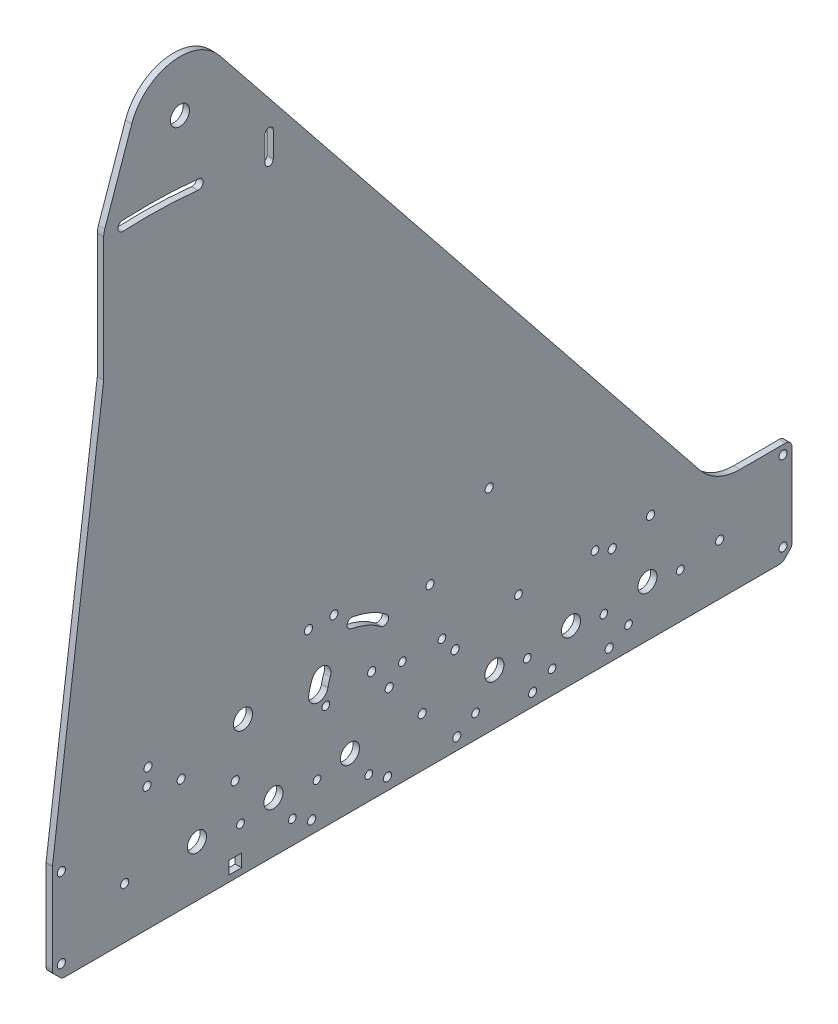
SolidWorks part; units mm, degrees
ref_plane "Front Plane" through (0, 0, 0) normal (0, 0, 1) x (1, 0, 0)
ref_plane "Top Plane" through (0, 0, 0) normal (0, 1, 0) x (1, 0, 0)
ref_plane "Right Plane" through (0, 0, 0) normal (1, 0, 0) x (0, 0, -1)
sketch "Sketch1" plane through (0, 0, 0) normal (1, 0, 0) x (0, 0, -1)
  line L0 (-184.15, -24.6062) -> (184.15, -24.6062)
  line L1 (184.15, -24.6062) -> (184.15, 26.1938)
  line L2 (184.15, 26.1938) -> (146.05, 26.1937)
  line L5 (-145.839, 321.5609) -> (-184.15, 26.1938)
  line L6 (-184.15, 26.1938) -> (-184.15, -24.6062)
  line L7 (-184.15, 350.0437) -> (184.15, 350.0437) construction
  line L9 (146.05, 26.1937) -> (-100.8314, 334.1803)
  arc A0 (-100.8314, 334.1803) -> (-145.839, 321.5609) centre (-120.65, 318.2937) ccw
  point P8 (0, -24.6062)
  dimension "D1" = 368.3
  dimension "D7" = 25.4
  dimension "D2" = 50.8
  dimension "D3" = 38.1
  dimension "D4" = 24.6062
  dimension "D5" = 374.65
  dimension "D6" = 304.8
  dimension "D8" = 342.9
extrude "Boss-Extrude1" add sketch "Sketch1" along normal blind 3.175
chamfer "Chamfer1" distance 4.7625 angle 45 2 edges at (1.5875, -24.6062, 184.15) (1.5875, -24.6062, -184.15)
fillet "Fillet1" radius 25.4 1 edges at (1.5875, 26.1937, -146.05)
fillet "Fillet2" radius 3.175 2 edges at (1.5875, 26.1938, 184.15) (1.5875, 26.1938, -184.15)
fillet "Fillet3" radius 3.175 4 edges at (1.5875, -19.8438, -184.15) (1.5875, -24.6062, -179.3875) (1.5875, -19.8437, 184.15) (1.5875, -24.6062, 179.3875)
sketch "Sketch30" plane through (3.175, 0, 0) normal (1, 0, 0) x (0, 0, -1)
  circle A8 centre (-89.211, 42.2593) radius 4.7625
  circle A9 centre (-25.1593, 30.6938) radius 2.032
  arc A10 (-51.7173, 35.4892) -> (-50.2741, 40.5715) centre (-25.1593, 30.6938) cw construction
  arc A11 (-54.7652, 42.3379) -> (-56.4665, 36.3468) centre (-25.1593, 30.6938) ccw
  arc A12 (-45.783, 38.8051) -> (-46.9681, 34.6317) centre (-25.1593, 30.6938) ccw
  arc A13 (-45.783, 38.8051) -> (-54.7652, 42.3379) centre (-50.2741, 40.5715) ccw
  arc A14 (-56.4665, 36.3468) -> (-46.9681, 34.6317) centre (-51.7173, 35.4892) ccw
  arc A15 (-34.9881, 56.6661) -> (-19.1131, 49.8125) centre (-41.7582, 19.1724) cw construction
  arc A16 (-17.6789, 51.753) -> (-34.5594, 59.0407) centre (-41.7582, 19.1724) ccw
  arc A17 (-20.5473, 47.8719) -> (-35.4169, 54.2915) centre (-41.7582, 19.1724) ccw
  arc A18 (-20.5473, 47.8719) -> (-17.6789, 51.753) centre (-19.1131, 49.8125) ccw
  arc A19 (-34.5594, 59.0407) -> (-35.4169, 54.2915) centre (-34.9881, 56.6661) ccw
  arc A20 (-19.1131, 49.8125) -> (-34.9881, 56.6661) centre (-41.7582, 19.1724) ccw construction
  circle A21 centre (94.6345, 23.8125) radius 2.032
  circle A22 centre (-56.6241, 64.5541) radius 2.032
  circle A23 centre (-43.9241, 64.5541) radius 2.032
  circle A24 centre (-56.6241, 64.5541) radius 1.905 construction
  circle A25 centre (-43.9241, 64.5541) radius 1.905 construction
  point P7 (-51.1204, 38.0658)
  point P19 (-26.6567, 54.1518)
  dimension "D2" = 9.652
  dimension "D4" = 4.064
  dimension "D1" = 4.064
  dimension ".375" = 9.525
  dimension "D3" = 4.826
extrude "Cut-Extrude9" cut sketch "Sketch30" against normal through all
sketch "Sketch16" plane through (3.175, 0, 0) normal (1, 0, 0) x (0, 0, -1)
  circle A0 centre (112.1746, 0.7937) radius 4.7625
  circle A1 centre (74.0746, 0.7937) radius 4.7625
  circle A2 centre (35.9746, 0.7937) radius 4.7625
  circle A3 centre (-35.9746, 0.7938) radius 4.7625
  circle A4 centre (-74.0746, 0.7938) radius 4.7625
  circle A5 centre (-112.1746, 0.7937) radius 4.7625
  dimension "D1" = 9.525
  dimension "D2" = 9.525
extrude "Cut-Extrude1" cut sketch "Sketch16" against normal up to next
sketch "Sketch25" plane through (3.175, 0, 0) normal (1, 0, 0) x (0, 0, -1)
  circle A0 centre (102.7672, -13.0003) radius 1.905 construction
  circle A1 centre (86.0486, 27.3622) radius 1.905 construction
  circle A2 centre (128.5804, -2.3081) radius 1.905 construction
  circle A3 centre (102.7672, -13.0003) radius 1.905
  circle A4 centre (86.0486, 27.3622) radius 1.905
  circle A5 centre (128.5804, -2.3081) radius 1.905
  circle A6 centre (64.6672, -13.0003) radius 1.905 construction
  circle A8 centre (-9.8486, 27.3622) radius 1.905 construction
  circle A10 centre (-47.9486, 27.3622) radius 1.905 construction
  circle A11 centre (-90.4804, -2.3081) radius 1.905 construction
  circle A12 centre (-64.6672, -13.0003) radius 1.905 construction
  circle A14 centre (-52.3804, -2.3081) radius 1.905 construction
  circle A15 centre (-26.5672, -13.0003) radius 1.905 construction
  circle A16 centre (9.8486, 27.3622) radius 1.905 construction
  circle A17 centre (26.5672, -13.0003) radius 1.905 construction
  circle A18 centre (47.9486, 27.3622) radius 1.905 construction
  circle A19 centre (52.3804, -2.3081) radius 1.905 construction
  circle A20 centre (90.4804, -2.3081) radius 1.905 construction
  circle A21 centre (-9.8486, 27.3622) radius 1.905
  circle A23 centre (-47.9486, 27.3622) radius 1.905
  circle A24 centre (-90.4804, -2.3081) radius 1.905
  circle A25 centre (-64.6672, -13.0003) radius 1.905
  circle A27 centre (-52.3804, -2.3081) radius 1.905
  circle A28 centre (-26.5672, -13.0003) radius 1.905
  circle A29 centre (9.8486, 27.3622) radius 1.905
  circle A30 centre (26.5672, -13.0003) radius 1.905
  circle A31 centre (47.9486, 27.3622) radius 1.905
  circle A32 centre (64.6672, -13.0003) radius 1.905
  circle A33 centre (52.3804, -2.3081) radius 1.905
  circle A34 centre (90.4804, -2.3081) radius 1.905
extrude "Cut-Extrude4" cut sketch "Sketch25" against normal up to next
sketch "Sketch23" plane through (3.175, 0, 0) normal (1, 0, 0) x (0, 0, -1)
  circle A0 centre (179.705, 21.7488) radius 1.905 construction
  point P0 (-55.0246, -18.3223)
  point P6 (-93.1246, 17.5943)
  point P9 (-17.2515, -18.6426)
  point P12 (-16.4124, 19.3854)
  point P15 (16.4124, 19.3854)
  point P18 (17.2515, -18.6426)
  point P21 (55.0246, -18.3223)
  point P35 (3.8736, 53.6853)
  point P38 (113.7728, 28.6594)
  point P41 (-137.0088, 37.226)
  point P44 (-179.705, 21.7487)
  point P47 (-179.705, -18.0026)
  point P50 (179.705, 21.7488)
  point P53 (179.705, -18.0026)
  point P59 (93.1246, -18.3223)
hole_wizard "#8 (0.16) Diameter Hole1" positions "Sketch23" profile "Sketch24" hole size "#8" standard "ANSI Inch" end condition up to next
sketch "Sketch24" plane through (3.175, -18.3223, 55.0246) normal (0, 1, 0) x (0, 0, -1)
  line L0 (0, 0) -> (0, 3.175)
  line L1 (0, 3.175) -> (2.032, 3.175)
  line L2 (2.032, 3.175) -> (2.032, 0)
  line L5 (2.032, 0) -> (0, 0)
  line L11 (0, -6.35) -> (0, 107.95) construction
  dimension "Thru Hole Dia." = 4.064
  dimension "Thru Hole Depth" = 3.175
sketch "Sketch22" plane through (3.175, 0, 0) normal (1, 0, 0) x (0, 0, -1)
  line L0 (-96.2996, -15.1473) -> (-89.9496, -15.1473) construction
  line L1 (-96.2996, -15.1473) -> (-89.9496, -15.1473)
  line L2 (-96.2996, -15.1473) -> (-96.2996, -21.4973)
  line L3 (-96.2996, -21.4973) -> (-89.9496, -21.4973)
  line L4 (-89.9496, -15.1473) -> (-89.9496, -21.4973)
  line L5 (-96.2996, -15.1473) -> (-89.9496, -21.4973) construction
  line L6 (-96.2996, -21.4973) -> (-89.9496, -15.1473) construction
  line L7 (-89.9496, -15.1473) -> (-89.9496, -19.8734) construction
  point P0 (-93.1246, -18.3223)
  dimension "D1" = 6.35
extrude "Cut-Extrude3" cut sketch "Sketch22" against normal up to next
sketch "Sketch21" plane through (3.175, 0, 0) normal (1, 0, 0) x (0, 0, -1)
  circle A0 centre (-148.1579, 0.7937) radius 2.032
  circle A2 centre (0, 0) radius 2.032
  circle A3 centre (148.1579, 0.7938) radius 2.032
  dimension "D1" = 4.064
extrude "Cut-Extrude2" cut sketch "Sketch21" against normal up to next
sketch "Sketch26" [suppressed] plane through (3.175, 0, 0) normal (1, 0, 0) x (0, 0, -1)
  line L0 (-145.839, 321.5609) -> (-184.1236, 26.3971) construction
  line L1 (-178.0724, -24.6062) -> (178.0724, -24.6062) construction
  circle A0 centre (-121.0218, 216.6937) radius 15.24
  dimension "D1" = 30.48
  dimension "D2" = 38.1
  dimension "D3" = 241.3
extrude "Cut-Extrude5" [suppressed] cut sketch "Sketch26" against normal through all
sketch "Sketch27" plane through (3.175, 0, 0) normal (1, 0, 0) x (0, 0, -1)
  circle A0 centre (-120.65, 318.2937) radius 4.7625
  dimension "D1" = 9.525
extrude "Cut-Extrude6" cut sketch "Sketch27" against normal through all
sketch "Sketch28" plane through (3.175, 0, 0) normal (1, 0, 0) x (0, 0, -1)
  line L0 (-120.65, 318.2937) -> (-103.5612, 277.2599) construction
  line L1 (-103.5612, 277.2599) -> (-86.3654, 258.566) construction
  line L2 (-86.3654, 258.566) -> (-90.1612, 246.4465) construction
  line L3 (-90.1612, 246.4465) -> (-93.9569, 234.327) construction
  line L4 (-145.839, 321.5609) -> (-184.1236, 26.3971) construction
  circle A0 centre (-93.9569, 234.327) radius 2.032
  circle A1 centre (-90.1612, 246.4465) radius 2.032
  circle A2 centre (-86.3654, 258.566) radius 2.0955
  circle A3 centre (-103.5612, 277.2599) radius 2.032
  dimension "D4" = 4.064
  dimension "D5" = 4.191
  dimension "D6" = 4.064
  dimension "D1" = 25.4
  dimension "D2" = 44.45
  dimension "D3" = 12.7
  dimension "D7" = 30
  dimension "D8" = 120
  dimension "D9" = 160
extrude "Cut-Extrude7" [suppressed] cut sketch "Sketch28" against normal through all
sketch "Sketch29" plane through (3.175, 0, 0) normal (1, 0, 0) x (0, 0, -1)
  line L1 (-76.2, 288.925) -> (-76.2, 276.225) construction
  line L2 (-74.168, 288.925) -> (-74.168, 276.225)
  line L3 (-78.232, 288.925) -> (-78.232, 276.225)
  arc A4 (-74.168, 288.925) -> (-78.232, 288.925) centre (-76.2, 288.925) ccw
  arc A5 (-78.232, 276.225) -> (-74.168, 276.225) centre (-76.2, 276.225) ccw
  point P8 (-76.2, 282.575)
  dimension "D1" = 276.225
  dimension "D2" = 2.032
  dimension "D3" = 76.2
  dimension "D4" = 12.7
sketch "Sketch31" plane through (0, 0, 0) normal (-1, 0, 0) x (0, 0, 1)
extrude "Cut-Extrude10" [suppressed] cut sketch "Sketch31" against normal through all
sketch "Sketch34" plane through (0, 0, 0) normal (-1, 0, 0) x (0, 0, 1)
  line L3 (123.9045, 95.7355) -> (127.1716, 70.5465) construction
  line L4 (126.0455, 96.0132) -> (129.3127, 70.8242)
  line L5 (121.7634, 95.4578) -> (125.0306, 70.2688)
  line L6 (145.839, 321.5609) -> (184.1236, 26.3971) construction
  arc A2 (126.0455, 96.0132) -> (121.7634, 95.4578) centre (123.9045, 95.7355) ccw
  arc A3 (125.0306, 70.2688) -> (129.3127, 70.8242) centre (127.1716, 70.5465) ccw
  point P9 (125.538, 83.141)
  dimension "D8" = 4.318
  dimension "D6" = 50.8
  dimension "D7" = 25.4
extrude "Cut-Extrude12" [suppressed] cut sketch "Sketch34" against normal through all
sketch "Sketch38" plane through (3.175, 0, 0) normal (1, 0, 0) x (0, 0, -1)
  line L0 (-184.15, 25.9887) -> (-184.15, -18.5286) construction
  line L1 (-178.0724, -24.6062) -> (178.0724, -24.6062) construction
  circle A0 centre (-136.525, 45.2437) radius 2.032
  dimension "D1" = 47.625
  dimension "D3" = 4.064
  dimension "D2" = 69.85
extrude "Cut-Extrude14" cut sketch "Sketch38" against normal through all
sketch "Sketch37" plane through (3.175, 0, 0) normal (1, 0, 0) x (0, 0, -1)
  circle A0 centre (33.3375, 80.645) radius 2.032
  circle A8 centre (0, 0) radius 2.032 construction
  dimension "D1" = 4.064
  dimension "D2" = 33.3375
  dimension "D3" = 80.645
extrude "Cut-Extrude13" cut sketch "Sketch37" against normal through all
extrude "Cut-Extrude15" cut sketch "Sketch29" against normal through all
sketch "Sketch40" plane through (3.175, 0, 0) normal (1, 0, 0) x (0, 0, -1)
  circle A0 centre (-120.015, 31.75) radius 2.032
  dimension "D1" = 4.064
  dimension "D2" = 120.015
  dimension "D3" = 31.75
extrude "Cut-Extrude16" cut sketch "Sketch40" against normal through all
sketch "Sketch41" [suppressed] plane through (3.175, 0, 0) normal (1, 0, 0) x (0, 0, -1)
  line L0 (-120.65, 318.2937) -> (-98.425, 279.7989) construction
  line L1 (-98.425, 279.7989) -> (-77.6666, 265.1617) construction
  line L2 (-120.65, 318.2937) -> (-60.41, 318.2937) construction
  circle A0 centre (-120.65, 318.2937) radius 25.4 construction
  circle A1 centre (-98.425, 279.7989) radius 19.05 construction
  circle A2 centre (-77.6666, 265.1617) radius 6.35 construction
  circle A3 centre (-98.425, 279.7989) radius 2.032
  circle A4 centre (-77.6666, 265.1617) radius 2.032
  dimension "D1" = 50.8
  dimension "D2" = 38.1
  dimension "D3" = 12.7
  dimension "D4" = 4.064
  dimension "D5" = 60
extrude "Cut-Extrude17" [suppressed] cut sketch "Sketch41" against normal through all
sketch "Sketch43" plane through (3.175, 0, 0) normal (1, 0, 0) x (0, 0, -1)
  line L0 (-152.4, 200.025) -> (-123.6487, 200.025) construction
  line L1 (-115.9779, 252.0412) -> (-152.4, 200.025) construction
  circle A0 centre (-152.4, 200.025) radius 2.032
  arc A1 (-143.2813, 262.8669) -> (-96.4668, 230.087) centre (-152.4, 200.025) cw construction
  arc A2 (-92.2158, 232.3717) -> (-142.5883, 267.6428) centre (-152.4, 200.025) ccw
  arc A3 (-100.7177, 227.8023) -> (-143.9743, 258.0909) centre (-152.4, 200.025) ccw
  arc A4 (-100.7177, 227.8023) -> (-92.2158, 232.3717) centre (-96.4668, 230.087) ccw
  arc A5 (-142.5883, 267.6428) -> (-143.9743, 258.0909) centre (-143.2813, 262.8669) ccw
  point P6 (-115.9779, 252.0412)
  dimension "D1" = 4.064
  dimension "D4" = 4.826
  dimension "D2" = 200.025
  dimension "D3" = 152.4
  dimension "D5" = 63.5
  dimension "D6" = 57.15
  dimension "D7" = 55
extrude "Cut-Extrude19" [suppressed] cut sketch "Sketch43" against normal through all
sketch "Sketch44" plane through (3.175, 0, 0) normal (1, 0, 0) x (0, 0, -1)
  circle A0 centre (-142.875, 226.3775) radius 2.032
  dimension "D1" = 4.064
  dimension "D2" = 142.875
  dimension "D3" = 226.3775
extrude "Cut-Extrude20" [suppressed] cut sketch "Sketch44" against normal through all
sketch "Sketch50" plane through (0, 0, 0) normal (-1, 0, 0) x (0, 0, 1)
  line L0 (89.6567, 207.1688) -> (64.2567, 207.1688) construction
  line L1 (89.6567, 205.1368) -> (64.2567, 205.1368)
  line L2 (89.6567, 209.2008) -> (64.2567, 209.2008)
  line L3 (64.2567, 194.4688) -> (38.8567, 194.4688) construction
  line L4 (64.2567, 192.4368) -> (38.8567, 192.4368)
  line L5 (64.2567, 196.5008) -> (38.8567, 196.5008)
  arc A1 (89.6567, 205.1368) -> (89.6567, 209.2008) centre (89.6567, 207.1688) ccw
  arc A2 (64.2567, 209.2008) -> (64.2567, 205.1368) centre (64.2567, 207.1688) ccw
  arc A3 (64.2567, 192.4368) -> (64.2567, 196.5008) centre (64.2567, 194.4688) ccw
  arc A4 (38.8567, 196.5008) -> (38.8567, 192.4368) centre (38.8567, 194.4688) ccw
  point P3 (76.9567, 207.1688)
  point P5 (51.5567, 194.4688)
  dimension "D1" = 2.032
  dimension "D2" = 207.1688
  dimension "D3" = 89.6567
  dimension "D4" = 25.4
  dimension "D5" = 12.7
extrude "Cut-Extrude22" [suppressed] cut sketch "Sketch50" against normal through all
sketch "Sketch51" plane through (3.175, 0, 0) normal (1, 0, 0) x (0, 0, -1)
  circle A0 centre (-111.125, 222.6469) radius 2.032
  circle A1 centre (-111.125, 190.8969) radius 2.032
  dimension "D1" = 222.6469
  dimension "D3" = 31.75
  dimension "D4" = 4.064
  dimension "D2" = 111.125
extrude "Cut-Extrude23" [suppressed] cut sketch "Sketch51" against normal through all
sketch "Sketch52" [suppressed] plane through (0, 0, 0) normal (-1, 0, 0) x (0, 0, 1)
  line L0 (145.839, 321.5609) -> (184.1236, 26.3971) construction
  line L1 (142.875, 226.3775) -> (142.0856, 251.7652) construction
  line L2 (120.4939, 238.3877) -> (142.875, 226.3775) construction
  arc A5 (142.0856, 251.7652) -> (120.4939, 238.3877) centre (142.875, 226.3775) ccw construction
  arc A6 (142.0224, 253.7962) -> (118.7034, 239.3485) centre (142.875, 226.3775) ccw
  arc A7 (142.1487, 249.7342) -> (122.2844, 237.4269) centre (142.875, 226.3775) ccw
  arc A8 (142.1487, 249.7342) -> (142.0224, 253.7962) centre (142.0856, 251.7652) ccw
  arc A9 (118.7034, 239.3485) -> (122.2844, 237.4269) centre (120.4939, 238.3877) ccw
  point P4 (129.4975, 247.9692)
  dimension "D1" = 25.4
  dimension "D2" = 2.032
  dimension "D3" = 12.7
  dimension "D4" = 60
extrude "Cut-Extrude24" [suppressed] cut sketch "Sketch52" against normal through all
sketch "Sketch53" plane through (3.175, 0, 0) normal (1, 0, 0) x (0, 0, -1)
  line L0 (-25.4, 197.2663) -> (-25.4, 135.876) construction
  line L1 (-23.368, 197.2663) -> (-23.368, 135.876)
  line L2 (-27.432, 197.2663) -> (-27.432, 135.876)
  arc A0 (-23.368, 197.2663) -> (-27.432, 197.2663) centre (-25.4, 197.2663) ccw
  arc A1 (-27.432, 135.876) -> (-23.368, 135.876) centre (-25.4, 135.876) ccw
  point P2 (-25.4, 166.5712)
  dimension "D1" = 2.032
  dimension "D2" = 61.3903
  dimension "D3" = 197.2663
  dimension "D4" = 25.4
extrude "Cut-Extrude25" [suppressed] cut sketch "Sketch53" against normal through all
sketch "Sketch56" plane through (3.175, 0, 0) normal (1, 0, 0) x (0, 0, -1)
  line L0 (-136.525, 285.2438) -> (-136.525, 45.2437) construction
  line L1 (-149.0856, 284.9148) -> (-136.525, 45.2437) construction
  line L2 (-136.525, 45.2437) -> (-111.4382, 283.929) construction
  arc A0 (-149.0856, 284.9148) -> (-111.4382, 283.929) centre (-136.525, 45.2437) cw
  point P5 (0, 0)
  dimension "D1" = 3
  dimension "D3" = 240
  dimension "D2" = 6
sketch "Sketch54" plane through (3.175, 0, 0) normal (1, 0, 0) x (0, 0, -1)
  line L0 (-145.839, 321.5609) -> (-184.1236, 26.3971) construction
  line L1 (-144.6368, 326.648) -> (-158.0807, 288.0477)
  line L2 (-145.839, 321.5609) -> (-158.6106, 223.0952)
  line L3 (-144.6368, 326.648) -> (-218.1381, 326.648) construction
  line L5 (-158.6106, 284.9148) -> (-158.6106, 223.0952)
  arc A1 (-100.8314, 334.1803) -> (-145.839, 321.5609) centre (-120.65, 318.2937) ccw construction
  arc A2 (-158.0807, 288.0477) -> (-158.6106, 284.9148) centre (-149.0856, 284.9148) ccw
  arc A3 (-144.6368, 326.648) -> (-145.839, 321.5609) centre (-120.65, 318.2937) ccw
  dimension "D1" = 9.525
extrude "Boss-Extrude2" add sketch "Sketch54" against normal up to surface (3.175 mm away) up to face at (0, 31.75, 117.983)
sketch "Sketch57" plane through (3.175, 0, 0) normal (1, 0, 0) x (0, 0, -1)
  arc A0 (-149.0856, 284.9148) -> (-111.4382, 283.929) centre (-136.525, 45.2437) cw construction
  arc A1 (-111.1859, 286.3288) -> (-149.2119, 287.3245) centre (-136.525, 45.2437) ccw
  arc A2 (-111.6904, 281.5292) -> (-148.9593, 282.5051) centre (-136.525, 45.2437) ccw
  arc A3 (-111.6904, 281.5292) -> (-111.1859, 286.3288) centre (-111.4382, 283.929) ccw
  arc A4 (-149.2119, 287.3245) -> (-148.9593, 282.5051) centre (-149.0856, 284.9148) ccw
  arc A5 (-111.4382, 283.929) -> (-149.0856, 284.9148) centre (-136.525, 45.2437) ccw construction
  point P3 (-130.2425, 285.1615)
  point P10 (-146.1175, 281.9865)
  dimension "D1" = 4.826
extrude "Cut-Extrude26" cut sketch "Sketch57" against normal up to next
